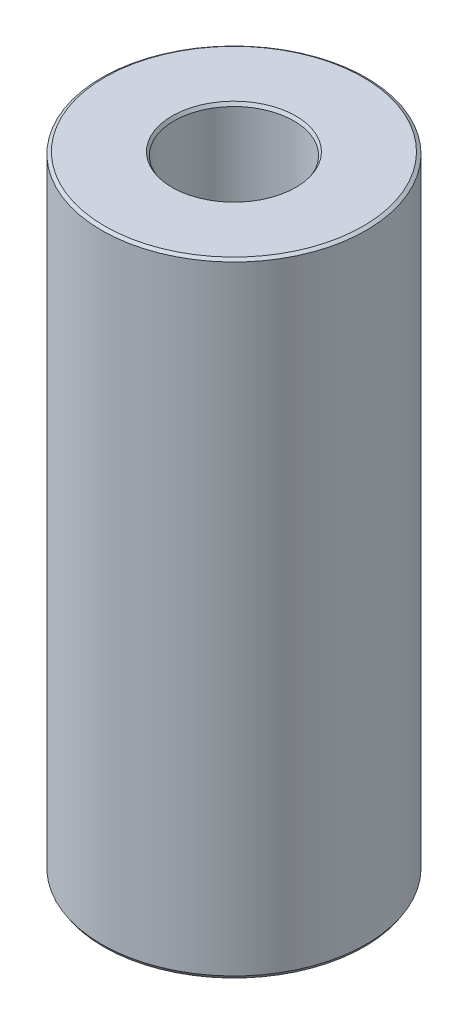
SolidWorks part; units mm, degrees
ref_plane "Front Plane" through (0, 0, 0) normal (0, 0, 1) x (1, 0, 0)
ref_plane "Top Plane" through (0, 0, 0) normal (0, 1, 0) x (1, 0, 0)
ref_plane "Right Plane" through (0, 0, 0) normal (1, 0, 0) x (0, 0, -1)
sketch "Sketch1" plane through (0, 0, 0) normal (0, 1, 0) x (1, 0, 0)
  circle A0 centre (0, 0) radius 60
  dimension "SLEEVE_OD" = 120
extrude "Boss-Extrude1" add sketch "Sketch1" along normal blind 282.78
sketch "Sketch2" plane through (0, 0, 0) normal (0, 1, 0) x (1, 0, 0)
  circle A0 centre (0, 0) radius 27.1559
  dimension "BORE_D" = 54.3119
extrude "Cut-Extrude1" cut sketch "Sketch2" along normal through all
chamfer "Chamfer1" distance 0.9152 angle 57.814 4 edges at (0, 282.78, 27.1559) (0, 0, 27.1559) (0, 0, 60) (0, 282.78, 60) first distance on face at (0, 282.78, 27.1559) first distance on face at (0, 0, 27.1559) first distance on face at (0, 282.78, 60)
